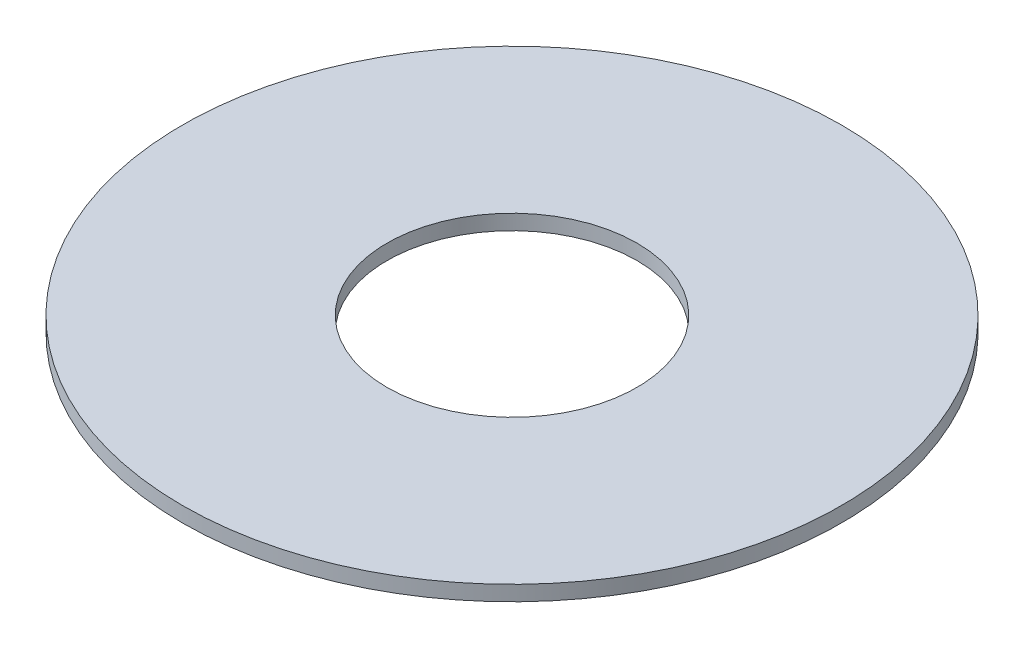
SolidWorks part; units mm, degrees
material "PTFE (general)"
ref_plane "Front Plane" through (0, 0, 0) normal (0, 0, 1) x (1, 0, 0)
ref_plane "Top Plane" through (0, 0, 0) normal (0, 1, 0) x (1, 0, 0)
ref_plane "Right Plane" through (0, 0, 0) normal (1, 0, 0) x (0, 0, -1)
sketch "Sketch1" plane through (0, 0, 0) normal (0, 1, 0) x (1, 0, 0)
  circle A0 centre (0, 0) radius 43.5
  circle A1 centre (0, 0) radius 16.5
  dimension "D1" = 33
  dimension "D2" = 87
extrude "Boss-Extrude1" add sketch "Sketch1" along normal blind 2
